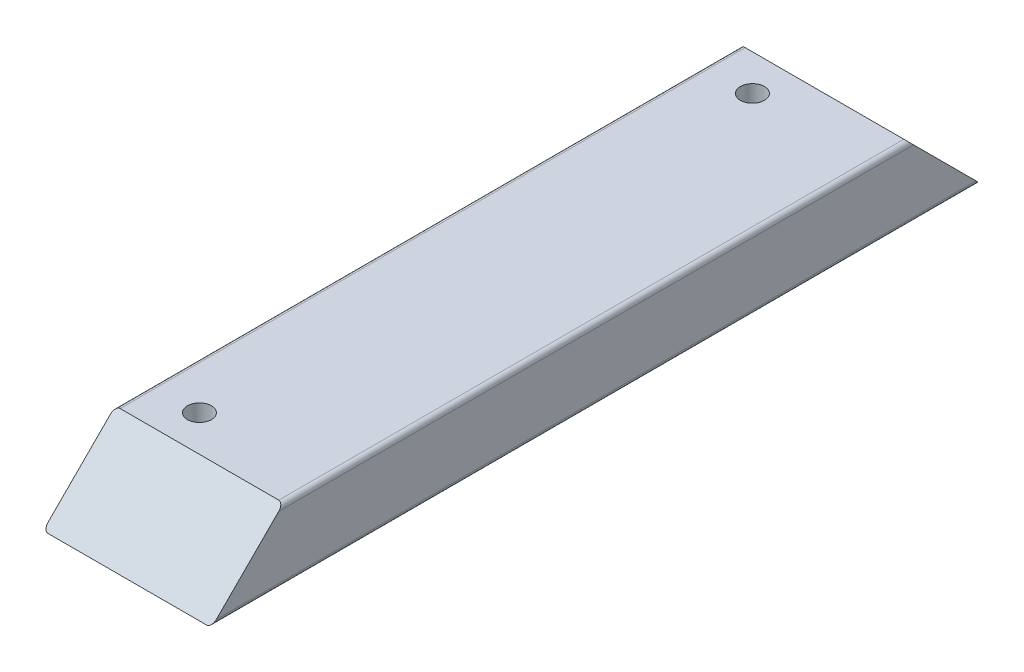
SolidWorks part; units mm, degrees
ref_plane "Front Plane" through (0, 0, 0) normal (0, 0, 1) x (1, 0, 0)
ref_plane "Top Plane" through (0, 0, 0) normal (0, 1, 0) x (1, 0, 0)
ref_plane "Right Plane" through (0, 0, 0) normal (1, 0, 0) x (0, 0, -1)
sketch "Sketch1" plane through (0, 0, 0) normal (0, 0, 1) x (1, 0, 0)
  line L1 (-44.45, 19.05) -> (44.45, 19.05)
  line L2 (-44.45, 19.05) -> (-44.45, -19.05)
  line L3 (-44.45, -19.05) -> (44.45, -19.05)
  line L4 (44.45, 19.05) -> (44.45, -19.05)
  line L5 (-44.45, 19.05) -> (44.45, -19.05) construction
  line L6 (-44.45, -19.05) -> (44.45, 19.05) construction
  point P0 (0, 0)
  dimension "D1" = 88.9
  dimension "D2" = 38.1
extrude "Boss-Extrude1" add sketch "Sketch1" along normal blind 406.4
fillet "Fillet1" radius 2.54 4 edges at (-44.45, -19.05, 203.2) (44.45, -19.05, 203.2) (44.45, 19.05, 203.2) (-44.45, 19.05, 203.2)
sketch "Sketch2" plane through (-44.45, 0, 0) normal (-1, 0, 0) x (0, 0, 1)
  line L0 (0, 19.05) -> (0, -19.05)
  line L1 (406.4, -19.05) -> (0, -19.05) construction
  line L2 (0, -16.51) -> (0, -19.05) construction
  line L3 (0, -19.05) -> (38.1, 19.05)
  line L4 (0, 19.05) -> (406.4, 19.05) construction
  line L5 (38.1, 19.05) -> (0, 19.05)
  dimension "D1" = 45
extrude "Cut-Extrude1" cut sketch "Sketch2" against normal blind 406.4
ref_plane "Plane1" through (0, 0, 203.2) normal (0, 0, 1) x (1, 0, 0)
mirror "Mirror1" about plane through (0, 0, 203.2) normal (0, 0, 1) of "Cut-Extrude1"
sketch "Sketch3" plane through (0, 19.05, 0) normal (0, 1, 0) x (1, 0, 0)
  line L0 (-44.45, -370.84) -> (-44.45, -35.56) construction
  line L1 (41.91, -38.1) -> (-41.91, -38.1) construction
  circle A0 centre (-19.05, -57.15) radius 6.35
  dimension "D2" = 12.7
  dimension "D1" = 25.4
  dimension "D3" = 19.05
extrude "Cut-Extrude2" cut sketch "Sketch3" against normal blind 406.4
mirror "Mirror4" about plane through (0, 0, 203.2) normal (0, 0, 1) of "Cut-Extrude2"
